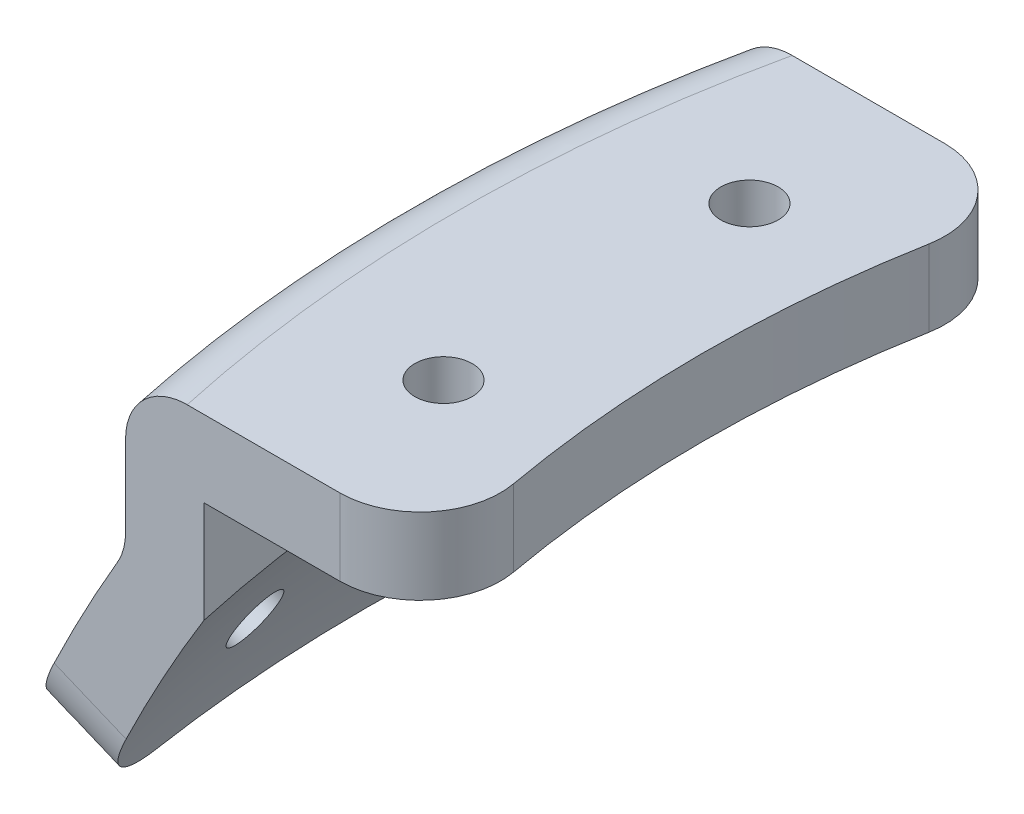
SolidWorks part; units mm, degrees
material "Polyether Polyol"
ref_plane "Front Plane" through (0, 0, 0) normal (0, 0, 1) x (1, 0, 0)
ref_plane "Top Plane" through (0, 0, 0) normal (0, 1, 0) x (1, 0, 0)
ref_plane "Right Plane" through (0, 0, 0) normal (1, 0, 0) x (0, 0, -1)
sketch "Sketch2" plane through (0, 0, 0) normal (0, 0, 1) x (1, 0, 0)
  line L0 (-196.1445, 172.2241) -> (-187.3619, 168.5374) construction
  line L1 (-183.6262, 216.8935) -> (-183.6262, 197.2811) construction
  line L2 (-174.1012, 207.3685) -> (-174.1012, 194.6685) construction
  line L3 (-145.5262, 207.3685) -> (-174.1012, 207.3685) construction
  line L4 (-145.5262, 207.3685) -> (-145.5262, 216.8935) construction
  line L5 (-145.5262, 216.8935) -> (-183.6262, 216.8935) construction
  line L6 (-196.1445, 172.2241) -> (-187.3619, 168.5374)
  line L7 (-183.6262, 216.8935) -> (-183.6262, 197.2811)
  line L8 (-174.1012, 207.3685) -> (-174.1012, 194.6685)
  line L9 (-145.5262, 207.3685) -> (-174.1012, 207.3685)
  line L10 (-145.5262, 207.3685) -> (-145.5262, 216.8935)
  line L11 (-145.5262, 216.8935) -> (-183.6262, 216.8935)
  line L12 (0, 0) -> (0, 215.8974) construction
  arc A0 (-183.6262, 197.2811) -> (-196.1445, 172.2241) centre (0, 89.8878) ccw construction
  arc A1 (-174.1012, 194.6685) -> (-187.3619, 168.5374) centre (0, 89.8878) ccw construction
  arc A2 (-183.6262, 197.2811) -> (-196.1445, 172.2241) centre (0, 89.8878) ccw
  arc A3 (-174.1012, 194.6685) -> (-187.3619, 168.5374) centre (0, 89.8878) ccw
revolve "Revolve1" add sketch "Sketch2" angle 30 mid plane about L12
fillet "Fillet1" radius 7.5 2 edges at (-183.6262, 197.2811, 0) (-183.6262, 216.8935, 0)
sketch "Sketch3" plane through (0, 207.3685, 0) normal (0, -1, 0) x (1, 0, 0)
  circle A0 centre (-158.75, 19.05) radius 3.5719 construction
  circle A1 centre (-158.75, -19.05) radius 3.5719 construction
  circle A2 centre (-158.75, 19.05) radius 3.5719
  circle A3 centre (-158.75, -19.05) radius 3.5719
extrude "Cut-Extrude1" cut sketch "Sketch3" against normal through all both and the other way through all
sketch "Sketch4" plane through (0, 216.8935, 0) normal (0, 1, 0) x (1, 0, 0)
  line L1 (-140.5675, 37.665) -> (-215.4275, 37.665)
  line L2 (-140.5675, 37.665) -> (-140.5675, -37.665)
  line L3 (-140.5675, -37.665) -> (-215.4275, -37.665)
  line L4 (-215.4275, 37.665) -> (-215.4275, -37.665)
extrude "Cut-Extrude2" cut sketch "Sketch4" against normal through all flip side to cut
fillet "Fillet2" radius 10 4 edges at (-140.5675, 212.131, -37.665) (-140.5675, 212.131, 37.665)
sketch "Sketch5" plane through (0, 0, 0) normal (0, 0, 1) x (1, 0, 0)
  line L0 (0, 89.8878) -> (-181.0525, 182.1386) construction
  line L1 (0, 0) -> (0, 215.8974) construction
  arc A1 (-174.1012, 194.6685) -> (-187.3619, 168.5374) centre (0, 89.8878) ccw construction
  dimension "D1" = 63
ref_plane "Plane1" through (36.3604, 71.3612, 0) normal (0.454, 0.891, 0) x (-0.891, 0.454, 0)
sketch "Sketch6" plane through (36.3604, 71.3612, 0) normal (0.454, 0.891, 0) x (-0.891, 0.454, 0)
  line L0 (216.8377, 18.9708) -> (270.6406, 23.678) construction
  line L1 (40.8082, 0) -> (244.0082, 0) construction
  line L2 (216.8377, 18.9708) -> (271.2422, 23.7306)
  line L3 (216.8377, 18.9708) -> (216.5264, 22.5291)
  line L4 (271.2422, 23.7306) -> (270.9309, 27.2889)
  line L5 (216.5264, 22.5291) -> (270.9309, 27.2889)
  dimension "D1" = 5
  dimension "D2" = 3.5719
revolve "Cut-Revolve1" cut sketch "Sketch6" angle 360 about L0
mirror "Mirror1" about plane through (0, 0, 0) normal (0, 0, 1) of "Cut-Revolve1"
